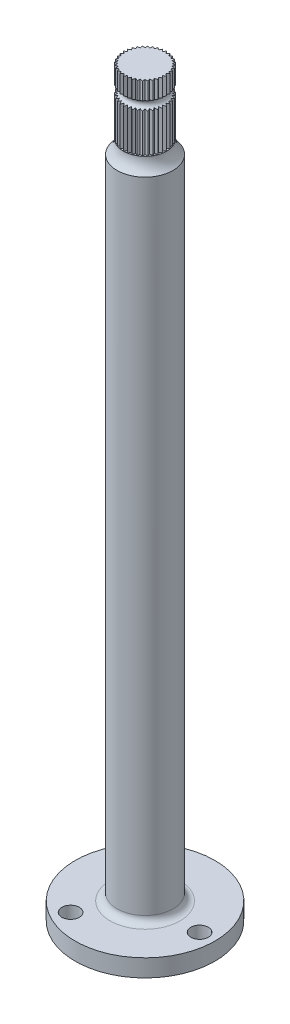
SolidWorks part; units mm, degrees
ref_plane "Front Plane" through (0, 0, 0) normal (0, 0, 1) x (1, 0, 0)
ref_plane "Top Plane" through (0, 0, 0) normal (0, 1, 0) x (1, 0, 0)
ref_plane "Right Plane" through (0, 0, 0) normal (1, 0, 0) x (0, 0, -1)
sketch "Sketch2" plane through (0, 0, 0) normal (0, 1, 0) x (1, 0, 0)
  circle A0 centre (0, 0) radius 10.16
extrude "Boss-Extrude1" add sketch "Sketch2" along normal blind 234.95
sketch "Sketch3" plane through (0, 234.95, 0) normal (0, 1, 0) x (1, 0, 0)
  circle A0 centre (0, 0) radius 7.874
  dimension "D1" = 15.748
extrude "Boss-Extrude2" add sketch "Sketch3" along normal blind 28.575
sketch "Sketch4" plane through (0, 0, 0) normal (0, 0, 1) x (1, 0, 0)
  line L0 (0, 263.525) -> (0, 239.7125)
  line L1 (7.874, 263.525) -> (-7.874, 263.525) construction
  dimension "D1" = 23.8125
  dimension "D2" = 0
fillet "Fillet1" radius 6.35 1 edges at (0, 234.95, 7.874)
sketch "Sketch5" plane through (0, 0, 0) normal (0, -1, 0) x (1, 0, 0)
  circle A0 centre (0, 0) radius 25.4
  dimension "D1" = 50.8
extrude "Boss-Extrude3" add sketch "Sketch5" along normal blind 6.35
fillet "Fillet2" radius 2.54 1 edges at (0, 0, 10.16)
sketch "Sketch15" plane through (0, 0, 0) normal (0, 0, 1) x (1, 0, 0)
  line L0 (0, 270.7847) -> (0, -23.9083) construction
sketch "Sketch16" plane through (0, -6.35, 0) normal (0, -1, 0) x (1, 0, 0)
  circle A0 centre (0, 0) radius 6.985
  circle A2 centre (19.812, 0) radius 3.175
  circle A3 centre (-9.906, 17.1577) radius 3.175
  circle A4 centre (-9.906, -17.1577) radius 3.175
  dimension "D1" = 13.97
sketch "Sketch18" plane through (0, 263.525, 0) normal (0, 1, 0) x (1, 0, 0)
  line L9 (0, 7.874) -> (-0.5774, 6.997)
  line L11 (0.0801, 7.9431) -> (0, 7.874)
  line L13 (-0.5774, 6.997) -> (-1.4202, 7.7449)
  line L14 (-1.4202, 7.7449) -> (-1.5641, 7.874)
  line L15 (-1.5641, 7.874) -> (0.1533, 8.0113)
  line L16 (0.1533, 8.0113) -> (0.0801, 7.9431)
  circle A0 centre (0, 0) radius 7.874 construction
  circle A1 centre (0, 0) radius 7.874 construction
extrude "Cut-Extrude13" cut sketch "Sketch18" against normal blind 23.622
pattern_circular "CirPattern2" count 36 every 10 about axis through (0, 270.7847, 0) along (0, -1, 0) of "Cut-Extrude13"
sketch "Sketch21" plane through (0, 0, 0) normal (0, 0, 1) x (1, 0, 0)
  line L0 (7.3726, 263.525) -> (6.3483, 263.525) construction
  circle A1 centre (7.9523, 255.5875) radius 1.5875
  dimension "D1" = 7.9375
  dimension "D2" = 3.175
revolve "Cut-Revolve1" cut sketch "Sketch21" angle 360 about L0
extrude "Cut-Extrude14" cut sketch "Sketch16" against normal blind 241.3
